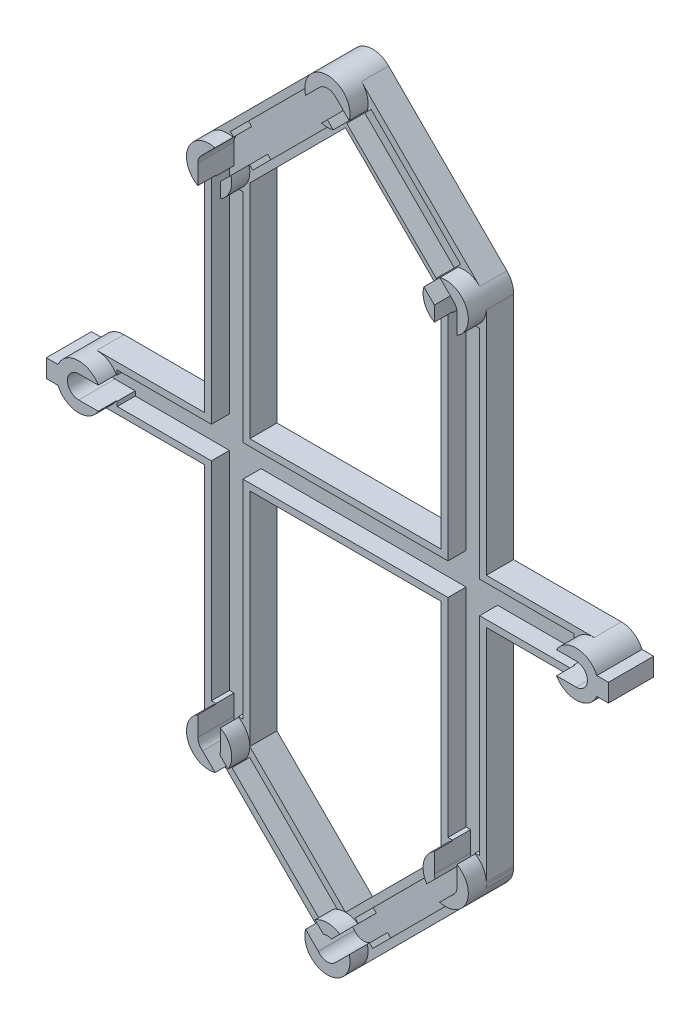
SolidWorks part; units mm, degrees
ref_plane "Спереди" through (0, 0, 0) normal (0, 0, 1) x (1, 0, 0)
ref_plane "Сверху" through (0, 0, 0) normal (0, 1, 0) x (1, 0, 0)
ref_plane "Справа" through (0, 0, 0) normal (1, 0, 0) x (0, 0, -1)
sketch "Эскиз1" plane through (0, 0, 0) normal (0, 0, 1) x (1, 0, 0)
  line L0 (-73.4107, 0) -> (65.3283, 0) construction
  line L1 (-12.0859, 54.2949) -> (-38.2489, 28.1319) construction
  line L2 (-12.0859, 54.2949) -> (14.077, 28.1319) construction
  line L3 (-38.2489, 0) -> (-38.2489, -121.4673) construction
  line L4 (14.077, 0) -> (14.077, -116.0096) construction
  line L5 (-38.2489, -81.8681) -> (14.077, -81.8681) construction
  line L6 (14.077, -81.8681) -> (-12.0859, -108.031) construction
  circle A0 centre (-12.0859, 54.2949) radius 2.5
  circle A1 centre (-12.0859, 54.2949) radius 5
  circle A2 centre (-38.2489, 28.1319) radius 2.5
  circle A3 centre (-38.2489, 28.1319) radius 5
  circle A4 centre (14.077, 28.1319) radius 2.5
  circle A5 centre (14.077, 28.1319) radius 5
  circle A6 centre (-38.2489, -81.8681) radius 2.5
  circle A7 centre (-38.2489, -81.8681) radius 5
  circle A8 centre (14.077, -81.8681) radius 2.5
  circle A9 centre (14.077, -81.8681) radius 5
  circle A10 centre (-12.0859, -108.031) radius 2.5
  circle A11 centre (-12.0859, -108.031) radius 5
  dimension "D2" = 5
  dimension "D3" = 10
  dimension "D5" = 45
  dimension "D1" = 45
  dimension "D4" = 37
  dimension "D6" = 37
  dimension "D7" = 110
  dimension "D8" = 110
  dimension "D9" = 37
  dimension "D10" = 45
  dimension "D11" = 37
extrude "Бобышка-Вытянуть1" add sketch "Эскиз1" along normal blind 10
sketch "Эскиз3" plane through (0, 0, 0) normal (0, 0, -1) x (-1, 0, 0)
  line L0 (12.0859, 54.2949) -> (15.6215, 57.8304)
  line L1 (15.6215, 57.8304) -> (41.7844, 31.6674)
  line L2 (41.7844, 31.6674) -> (34.7133, 24.5964)
  line L3 (34.7133, 24.5964) -> (8.5504, 50.7593)
  line L4 (8.5504, 50.7593) -> (12.0859, 54.2949)
  circle A0 centre (12.0859, 54.2949) radius 5 construction
  circle A1 centre (38.2489, 28.1319) radius 5 construction
extrude "Бобышка-Вытянуть2" add sketch "Эскиз3" against normal blind 6
sketch "Эскиз4" plane through (0, 0, 6) normal (0, 0, 1) x (1, 0, 0)
  line L0 (-13.8537, 56.0626) -> (-10.3181, 52.5271)
  line L1 (-13.8537, 56.0626) -> (-10.3181, 52.5271) construction
  line L2 (-10.3181, 52.5271) -> (-36.4811, 26.3641)
  line L3 (-36.4811, 26.3641) -> (-40.0166, 29.8997) construction
  line L4 (-36.4811, 26.3641) -> (-40.0166, 29.8997)
  line L5 (-40.0166, 29.8997) -> (-13.8537, 56.0626)
  line L6 (-8.5504, 50.7593) -> (-34.7133, 24.5964) construction
  line L8 (-41.7844, 31.6674) -> (-15.6215, 57.8304) construction
  dimension "D1" = 2.5
  dimension "D2" = 2.5
sketch "Эскиз9" plane through (0, 0, 0) normal (0, 0, -1) x (-1, 0, 0)
  line L0 (-14.077, 28.1319) -> (-17.6126, 31.6674)
  line L1 (-17.6126, 31.6674) -> (8.5504, 57.8304)
  line L2 (8.5504, 57.8304) -> (15.6215, 50.7593)
  line L3 (15.6215, 50.7593) -> (-10.5415, 24.5964)
  line L4 (-10.5415, 24.5964) -> (-14.077, 28.1319)
  circle A0 centre (-14.077, 28.1319) radius 5 construction
  arc A1 (15.6215, 57.8304) -> (8.5504, 50.7593) centre (12.0859, 54.2949) ccw construction
extrude "Бобышка-Вытянуть4" add sketch "Эскиз9" against normal blind 6
extrude "Вырез-Вытянуть1" cut sketch "Эскиз4" against normal blind 4
sketch "Эскиз5" plane through (0, 0, 0) normal (0, 0, -1) x (-1, 0, 0)
  line L0 (13.8537, 56.0626) -> (12.0859, 54.2949) construction
  line L1 (36.4811, 26.3641) -> (40.0166, 29.8997) construction
  circle A0 centre (12.9698, 55.1787) radius 3.75
  circle A1 centre (38.2489, 28.1319) radius 2.5
  arc A2 (36.4811, 26.3641) -> (40.0166, 29.8997) centre (38.2489, 28.1319) ccw construction
  arc A3 (13.8537, 56.0626) -> (10.3181, 56.0626) centre (12.0859, 54.2949) ccw construction
extrude "Бобышка-Вытянуть3" add sketch "Эскиз5" against normal blind 2
extrude "Вырез-Вытянуть2" cut sketch "Эскиз4<2>" along normal blind 4
sketch "Эскиз4<2>" plane through (0, 0, 6) normal (0, 0, 1) x (1, 0, 0) same geometry as "Эскиз4"
sketch "Эскиз10" plane through (0, 0, 10) normal (0, 0, 1) x (1, 0, 0)
  line L0 (14.077, 28.1319) -> (12.3093, 26.3641)
  line L1 (12.3093, 26.3641) -> (-13.8537, 52.5271)
  line L2 (-13.8537, 52.5271) -> (-12.0859, 54.2949)
  line L3 (-12.0859, 54.2949) -> (-10.3181, 56.0626)
  line L4 (-10.3181, 56.0626) -> (15.8448, 29.8997)
  line L5 (15.8448, 29.8997) -> (14.077, 28.1319)
  circle A0 centre (14.077, 28.1319) radius 2.5 construction
  arc A1 (-10.3181, 52.5271) -> (-13.8537, 56.0626) centre (-12.0859, 54.2949) ccw construction
extrude "Вырез-Вытянуть3" cut sketch "Эскиз10" against normal blind 8
sketch "Эскиз11" plane through (0, 0, 0) normal (0, 0, -1) x (-1, 0, 0)
  line L0 (-15.8448, 29.8997) -> (-12.3093, 26.3641) construction
  circle A0 centre (-14.077, 28.1319) radius 2.5
  arc A1 (-15.8448, 29.8997) -> (-12.3093, 26.3641) centre (-14.077, 28.1319) ccw construction
extrude "Бобышка-Вытянуть9" add sketch "Эскиз11" against normal blind 2
sketch "Skizze2" plane through (0, 0, 0) normal (0, 0, -1) x (-1, 0, 0)
  line L0 (-19.0722, 27.9121) -> (-19.0722, -82.053)
  line L1 (-18.9492, -82.9917) -> (-17.9635, -85.0138)
  line L2 (-17.9635, -85.0138) -> (8.5504, -111.5666)
  line L3 (8.5504, -111.5666) -> (15.6215, -111.5666)
  line L4 (15.6215, -111.5666) -> (41.7844, -85.4037)
  line L5 (41.7844, -85.4037) -> (43.2489, -81.8681)
  line L6 (43.2489, -81.8681) -> (43.2489, 28.1319)
  line L7 (33.2489, -81.8681) -> (33.2489, 26.0608)
  line L8 (12.0859, 47.2238) -> (34.7133, 24.5964) construction
  line L9 (33.2489, 26.0608) -> (43.2489, 28.1319)
  line L10 (33.2489, -81.8681) -> (12.0859, -103.031)
  line L11 (12.0859, -103.031) -> (-9.077, -81.8681)
  line L12 (-9.077, -81.8681) -> (-9.077, 26.0608)
  line L13 (-10.5415, 24.5964) -> (12.0859, 47.2238) construction
  line L14 (-9.077, 26.0608) -> (-19.0722, 27.9121)
  arc A0 (-17.6126, 31.6674) -> (-10.5415, 24.5964) centre (-14.077, 28.1319) ccw construction
  arc A1 (-19.0722, -82.053) -> (-18.9492, -82.9917) centre (-15.4304, -82.053) ccw
  circle A2 centre (-14.077, -81.8681) radius 5 construction
  circle A3 centre (12.0859, -108.031) radius 5 construction
  circle A4 centre (38.2489, -81.8681) radius 5 construction
  arc A5 (34.7133, 24.5964) -> (41.7844, 31.6674) centre (38.2489, 28.1319) ccw construction
extrude "Aufsatz-Linear austragen1" add sketch "Skizze2" against normal blind 6
sketch "Skizze4" plane through (0, 0, 10) normal (0, 0, 1) x (1, 0, 0)
  line L0 (11.577, -22.0611) -> (16.577, -22.0611)
  line L1 (16.577, -22.0611) -> (16.577, -81.8681)
  line L2 (16.577, -81.8681) -> (11.577, -81.8681)
  line L3 (11.577, -81.8681) -> (11.577, -22.0611)
  circle A0 centre (14.077, -81.8681) radius 2.5 construction
  circle A1 centre (14.077, -81.8681) radius 2.5 construction
extrude "Schnitt-Linear austragen1" cut sketch "Skizze4" against normal blind 8
sketch "Skizze5" plane through (0, 0, 10) normal (0, 0, 1) x (1, 0, 0)
  line L0 (-38.2489, -81.8681) -> (-35.7489, -81.8681)
  line L1 (-35.7489, -81.8681) -> (-35.7489, 28.1319)
  line L2 (-38.2489, -81.8681) -> (-40.7489, -81.8681)
  line L3 (-40.7489, -81.8681) -> (-40.7489, 28.1319)
  line L4 (-40.7489, 28.1319) -> (-35.7489, 28.1319)
  circle A0 centre (-38.2489, -81.8681) radius 2.5 construction
  arc A1 (-40.0166, 29.8997) -> (-40.6921, 27.6024) centre (-38.2489, 28.1319) ccw construction
extrude "Schnitt-Linear austragen2" cut sketch "Skizze5" against normal blind 8
sketch "Skizze6" plane through (0, 0, 10) normal (0, 0, 1) x (1, 0, 0)
  line L0 (-12.8158, -107.3468) -> (13.706, -80.7861)
  line L2 (13.706, -80.7861) -> (16.1827, -83.2591)
  line L3 (16.1827, -83.2591) -> (-10.3391, -109.8198)
  line L5 (-10.3391, -109.8198) -> (-12.8158, -107.3468)
  line L6 (17.2285, -85.7499) -> (-8.5478, -111.564) construction
  dimension "D1" = 2.5
  dimension "D2" = 3.5
extrude "Schnitt-Linear austragen3" cut sketch "Skizze6" against normal blind 8
sketch "Skizze8" plane through (0, 0, 10) normal (0, 0, 1) x (1, 0, 0)
  line L0 (-37.3688, -81.2837) -> (-11.1862, -107.4663)
  line L1 (-11.1862, -107.4663) -> (-13.6611, -109.9412)
  line L2 (-13.6611, -109.9412) -> (-39.8437, -83.7585)
  line L3 (-39.8437, -83.7585) -> (-37.3688, -81.2837)
  line L5 (-33.2489, -81.8681) -> (-12.0859, -103.031) construction
  dimension "D1" = 2.5
  dimension "D2" = 3.5
extrude "Schnitt-Linear austragen6" cut sketch "Skizze8" against normal blind 8
sketch "Skizze9" plane through (0, 0, 10) normal (0, 0, 1) x (1, 0, 0)
  line L1 (16.577, -22.0611) -> (11.577, -22.0611)
  line L2 (16.577, -22.0611) -> (16.577, 28.2549)
  line L3 (16.577, 28.2549) -> (11.577, 28.2549)
  line L4 (11.577, -22.0611) -> (11.577, 28.2549)
extrude "Schnitt-Linear austragen8" cut sketch "Skizze9" against normal blind 8
sketch "Skizze10" plane through (0, 0, 6) normal (0, 0, 1) x (1, 0, 0)
  line L2 (11.7397, -82.7552) -> (12.6255, -81.8681)
  line L3 (12.6255, -81.8681) -> (11.577, -81.8681)
  line L4 (11.7397, -82.7552) -> (12.6255, -81.8681)
  line L5 (12.6255, -81.8681) -> (11.577, -81.8681)
  line L6 (14.7896, -81.8681) -> (16.1656, -83.2421)
  line L7 (16.577, -81.8681) -> (14.7896, -81.8681)
  line L8 (14.7896, -81.8681) -> (16.1656, -83.2421)
  line L9 (16.577, -81.8681) -> (14.7896, -81.8681)
  line L10 (-12.9627, -105.6898) -> (-12.0613, -106.5912)
  line L11 (-12.0613, -106.5912) -> (-11.1745, -105.7031)
  line L12 (-12.9627, -105.6898) -> (-12.0613, -106.5912)
  line L13 (-12.0613, -106.5912) -> (-11.1745, -105.7031)
  line L14 (-36.7844, -81.8681) -> (-35.9076, -82.7448)
  line L15 (-11.9406, -108.2207) -> (-13.6611, -109.9412)
  line L16 (-13.6611, -109.9412) -> (-14.1255, -109.4767)
  line L17 (-10.3393, -109.8197) -> (-11.9406, -108.2207)
  line L18 (-11.9406, -108.2207) -> (-13.6611, -109.9412)
  line L19 (-13.6611, -109.9412) -> (-14.1255, -109.4767)
  line L20 (-10.3393, -109.8197) -> (-11.9406, -108.2207)
  line L21 (-39.8437, -83.7585) -> (-37.9533, -81.8681)
  line L22 (-37.9533, -81.8681) -> (-40.7489, -81.8681)
  line L23 (-39.6945, -83.9077) -> (-39.8437, -83.7585)
  line L24 (-39.8437, -83.7585) -> (-37.9533, -81.8681)
  line L25 (-37.9533, -81.8681) -> (-40.7489, -81.8681)
  line L26 (-39.6945, -83.9077) -> (-39.8437, -83.7585)
  line L27 (-35.7489, -81.8681) -> (-36.7844, -81.8681)
  line L28 (-36.7844, -81.8681) -> (-35.9076, -82.7448)
  line L29 (-35.7489, -81.8681) -> (-36.7844, -81.8681)
  arc A1 (11.577, -81.8681) -> (11.7397, -82.7552) centre (14.077, -81.8681) ccw
  arc A2 (11.577, -81.8681) -> (11.7397, -82.7552) centre (14.077, -81.8681) ccw
  arc A3 (16.1656, -83.2421) -> (16.577, -81.8681) centre (14.077, -81.8681) ccw
  arc A4 (16.1656, -83.2421) -> (16.577, -81.8681) centre (14.077, -81.8681) ccw
  arc A5 (-11.1745, -105.7031) -> (-12.9627, -105.6898) centre (-12.0859, -108.031) ccw
  arc A6 (-11.1745, -105.7031) -> (-12.9627, -105.6898) centre (-12.0859, -108.031) ccw
  arc A7 (-14.1255, -109.4767) -> (-10.3393, -109.8197) centre (-12.0859, -108.031) ccw
  arc A8 (-14.1255, -109.4767) -> (-10.3393, -109.8197) centre (-12.0859, -108.031) ccw
  arc A9 (-40.7489, -81.8681) -> (-39.6945, -83.9077) centre (-38.2489, -81.8681) ccw
  arc A10 (-40.7489, -81.8681) -> (-39.6945, -83.9077) centre (-38.2489, -81.8681) ccw
  arc A11 (-35.9076, -82.7448) -> (-35.7489, -81.8681) centre (-38.2489, -81.8681) ccw
  arc A12 (-35.9076, -82.7448) -> (-35.7489, -81.8681) centre (-38.2489, -81.8681) ccw
  dimension "D1" = 0
  dimension "D2" = 0
  dimension "D3" = 0
  dimension "D4" = 0
  dimension "D5" = 0
  dimension "D6" = 0
extrude "Schnitt-Linear austragen9" cut sketch "Skizze10" against normal blind 4
sketch "Skizze11" plane through (0, 0, 0) normal (0, 0, -1) x (-1, 0, 0)
  line L0 (12.0859, 47.2238) -> (12.0859, -103.031) construction
  line L2 (-42.9141, -22.9036) -> (67.0859, -22.9036)
  line L3 (-42.9141, -22.9036) -> (-42.9141, -32.9036)
  line L4 (-42.9141, -32.9036) -> (67.0859, -32.9036)
  line L5 (12.0859, 47.2238) -> (33.2489, 26.0608) construction
  line L6 (67.0859, -22.9036) -> (67.0859, -32.9036)
  point P9 (12.0859, -27.9036)
  dimension "D1" = 5
  dimension "D2" = 90
  dimension "D3" = 55
  dimension "D4" = 10
  dimension "D5" = 110
extrude "Aufsatz-Linear austragen2" add sketch "Skizze11" against normal blind 6
sketch "Skizze12" plane through (0, 0, 0) normal (0, 0, -1) x (-1, 0, 0)
  line L0 (67.0859, -22.9036) -> (43.2489, -22.9036) construction
  line L1 (67.0859, -32.9036) -> (67.0859, -22.9036) construction
  line L2 (-42.9141, -22.9036) -> (-42.9141, -32.9036) construction
  line L3 (-42.9141, -32.9036) -> (-19.0722, -32.9036) construction
  circle A0 centre (-42.9141, -27.9036) radius 2.5
  circle A1 centre (-42.9141, -27.9036) radius 5
  circle A2 centre (67.0859, -27.9036) radius 2.5
  circle A3 centre (67.0859, -27.9036) radius 5
  dimension "D1" = 5
  dimension "D2" = 10
  dimension "D5" = 5
  dimension "D6" = 10
  dimension "D3" = 5
  dimension "D4" = 0
  dimension "D7" = 0
  dimension "D8" = 5
extrude "Aufsatz-Linear austragen4" add sketch "Skizze12" against normal blind 10
sketch "Skizze15" plane through (0, 0, 10) normal (0, 0, 1) x (1, 0, 0)
  line L0 (42.9141, -30.4036) -> (16.602, -30.4036)
  line L1 (16.602, -30.4036) -> (16.577, -32.9036)
  line L2 (16.577, -32.9036) -> (11.577, -32.9036)
  line L3 (11.577, -32.9036) -> (11.577, -81.8681) construction
  line L4 (16.577, -32.9036) -> (11.577, -32.9036) construction
  line L5 (11.577, -32.9036) -> (11.577, -30.4036)
  line L6 (11.577, -30.4036) -> (-35.7489, -30.4036)
  line L7 (-35.7489, -30.4036) -> (-35.7489, -32.9036)
  line L8 (-35.7489, -32.9036) -> (-40.7489, -32.9036)
  line L9 (-40.7489, -32.9036) -> (-40.7489, -30.4036)
  line L10 (-40.7489, -30.4036) -> (-67.0859, -30.4036)
  line L11 (-67.0859, -30.4036) -> (-67.0859, -25.4036)
  line L12 (-67.0859, -25.4036) -> (-40.7489, -25.4036)
  line L13 (-40.7489, -25.4036) -> (-40.7489, -22.9036)
  line L14 (-40.7489, -22.9036) -> (-35.7489, -22.9036)
  line L15 (-35.7489, -22.9036) -> (-35.7489, -25.4036)
  line L16 (-35.7489, -25.4036) -> (11.577, -25.4036)
  line L17 (11.577, -25.4036) -> (11.577, -22.9036)
  line L18 (11.577, -22.9036) -> (16.577, -22.9036)
  line L19 (16.577, -22.9036) -> (16.577, -25.4036)
  line L20 (16.577, -25.4036) -> (42.9141, -25.4036)
  line L21 (42.9141, -25.4036) -> (42.9141, -30.4036)
  circle A0 centre (-67.0859, -27.9036) radius 2.5 construction
  arc A1 (-67.0859, -30.4036) -> (-67.0859, -25.4036) centre (-67.0859, -27.9036) ccw construction
extrude "Schnitt-Linear austragen10" cut sketch "Skizze15" against normal blind 8
sketch "Skizze16" plane through (0, 0, 0) normal (0, 0, -1) x (-1, 0, 0)
  line L0 (67.0859, -30.4036) -> (67.0859, -25.4036) construction
  line L1 (67.0859, -30.4036) -> (67.0859, -25.4036)
  line L2 (-42.9141, -25.4036) -> (-42.9141, -30.4036) construction
  line L3 (-42.9141, -25.4036) -> (-42.9141, -30.4036)
  arc A0 (67.0859, -30.4036) -> (67.0859, -25.4036) centre (67.0859, -27.9036) ccw construction
  arc A1 (67.0859, -30.4036) -> (67.0859, -25.4036) centre (67.0859, -27.9036) ccw
  arc A2 (-42.9141, -25.4036) -> (-42.9141, -30.4036) centre (-42.9141, -27.9036) ccw construction
  arc A3 (-42.9141, -25.4036) -> (-42.9141, -30.4036) centre (-42.9141, -27.9036) ccw
extrude "Aufsatz-Linear austragen5" add sketch "Skizze16" against normal blind 2
sketch "Skizze17" plane through (0, 0, 0) normal (0, 0, -1) x (-1, 0, 0)
  line L0 (-19.0722, -22.9036) -> (-42.9141, -22.9036) construction
  line L1 (-47.0722, -25.9036) -> (-50.0722, -25.9036)
  line L2 (-47.0722, -25.9036) -> (-47.0722, -29.9036)
  line L3 (-47.0722, -29.9036) -> (-50.0722, -29.9036)
  line L4 (-50.0722, -25.9036) -> (-50.0722, -29.9036)
  line L5 (-42.9141, -32.9036) -> (-19.0722, -32.9036) construction
  line L6 (-19.0722, -32.9036) -> (-19.0722, -81.6482) construction
  line L7 (67.0859, -22.9036) -> (43.2489, -22.9036) construction
  line L8 (71.2489, -25.9036) -> (74.2489, -25.9036)
  line L9 (71.2489, -25.9036) -> (71.2489, -29.9036)
  line L10 (71.2489, -29.9036) -> (74.2489, -29.9036)
  line L11 (74.2489, -25.9036) -> (74.2489, -29.9036)
  line L12 (43.2489, -32.9036) -> (67.0859, -32.9036) construction
  line L13 (43.2489, -81.8681) -> (43.2489, -32.9036) construction
  dimension "D1" = 3
  dimension "D2" = 3
  dimension "D3" = 28
  dimension "D4" = 3
  dimension "D5" = 3
  dimension "D6" = 3
  dimension "D7" = 28
  dimension "D8" = 3
extrude "Aufsatz-Linear austragen6" add sketch "Skizze17" against normal blind 10
sketch "Skizze18" plane through (0, 0, 6) normal (0, 0, 1) x (1, 0, 0)
  line L0 (-43.2489, -32.9036) -> (-67.0859, -32.9036) construction
  line L1 (38.4141, -24.4036) -> (-62.5764, -24.4036)
  line L2 (38.4141, -24.4036) -> (38.4141, -31.4036)
  line L3 (38.4141, -31.4036) -> (-62.5764, -31.4036)
  line L4 (-62.5764, -24.4036) -> (-62.5764, -31.4036)
  line L5 (-67.0859, -22.9036) -> (-43.2489, -22.9036) construction
  arc A0 (-67.0859, -25.4036) -> (-67.0859, -30.4036) centre (-67.0859, -27.9036) ccw construction
  arc A1 (42.9141, -30.4036) -> (42.9141, -25.4036) centre (42.9141, -27.9036) ccw construction
  point P11 (-69.5859, -27.9036)
  dimension "D1" = 1.5
  dimension "D2" = 1.5
  dimension "D3" = 7.0096
  dimension "D4" = 4.5
extrude "Schnitt-Linear austragen11" cut sketch "Skizze18" against normal blind 4
sketch "Skizze19" plane through (0, 0, 6) normal (0, 0, 1) x (1, 0, 0)
  line L0 (-33.2489, 26.0608) -> (-33.2489, -22.9036) construction
  line L1 (-34.7489, 23.6319) -> (-41.7489, 23.6319)
  line L2 (-34.7489, 23.6319) -> (-34.7489, -77.3681)
  line L3 (-34.7489, -77.3681) -> (-41.7489, -77.3681)
  line L4 (-41.7489, 23.6319) -> (-41.7489, -77.3681)
  line L5 (-43.2489, -22.9036) -> (-43.2489, 28.1319) construction
  line L6 (19.0722, 27.9121) -> (19.0722, -22.9036) construction
  line L7 (17.5722, 23.6319) -> (10.577, 23.6319)
  line L8 (17.5722, 23.6319) -> (17.5722, -77.3681)
  line L9 (17.5722, -77.3681) -> (10.577, -77.3681)
  line L10 (10.577, 23.6319) -> (10.577, -77.3681)
  line L11 (9.077, -22.9036) -> (9.077, 26.0608) construction
  arc A0 (-36.9548, 32.9615) -> (-40.7489, 23.8018) centre (-38.2489, 28.1319) ccw construction
  arc A1 (-40.7489, -77.538) -> (-36.9153, -86.687) centre (-38.2489, -81.8681) ccw construction
  arc A2 (16.577, 23.8018) -> (12.7829, 32.9615) centre (14.077, 28.1319) ccw construction
  arc A3 (12.7563, -86.6905) -> (16.577, -77.538) centre (14.077, -81.8681) ccw construction
  dimension "D1" = 1.5
  dimension "D2" = 1.5
  dimension "D3" = 4.5
  dimension "D4" = 4.5
  dimension "D5" = 1.5
  dimension "D6" = 1.5
  dimension "D7" = 4.5
  dimension "D8" = 4.5
extrude "Schnitt-Linear austragen12" cut sketch "Skizze19" against normal blind 4
sketch "Skizze20" plane through (0, 0, 6) normal (0, 0, 1) x (1, 0, 0)
  line L0 (13.3549, -87.5063) -> (-6.0763, -106.966)
  line L1 (-6.0763, -106.966) -> (-9.9682, -103.0797)
  line L2 (-9.9682, -103.0797) -> (9.4629, -83.6201)
  line L3 (9.4629, -83.6201) -> (13.3549, -87.5063)
  line L4 (17.2285, -85.7499) -> (-8.5478, -111.564) construction
  line L6 (-33.274, -83.9643) -> (-13.8286, -103.4097)
  line L7 (-13.8286, -103.4097) -> (-17.7428, -107.3239)
  line L8 (-17.7428, -107.3239) -> (-37.1882, -87.8785)
  line L9 (-37.1882, -87.8785) -> (-33.274, -83.9643)
  line L10 (-33.2489, -81.8681) -> (-12.0859, -103.031) construction
  line L11 (-15.6215, -111.5666) -> (-41.7844, -85.4037) construction
  arc A0 (12.7563, -86.6905) -> (16.577, -77.538) centre (14.077, -81.8681) ccw construction
  arc A1 (-16.9048, -106.6975) -> (-7.2572, -106.7334) centre (-12.0859, -108.031) ccw construction
  arc A2 (-40.7489, -77.538) -> (-36.9153, -86.687) centre (-38.2489, -81.8681) ccw construction
  dimension "D1" = 1.5
  dimension "D2" = 4.5
  dimension "D3" = 5.5
  dimension "D4" = 5
  dimension "D5" = 1.5
  dimension "D6" = 1.5
  dimension "D7" = 4.5
  dimension "D8" = 5
extrude "Schnitt-Linear austragen13" cut sketch "Skizze20" against normal blind 4
sketch "Skizze21" plane through (0, 0, 6) normal (0, 0, 1) x (1, 0, 0)
  line L0 (-11.8121, 48.2047) -> (7.9869, 28.4057)
  line L1 (7.9869, 28.4057) -> (13.3699, 33.7888)
  line L2 (13.3699, 33.7888) -> (-6.4291, 53.5878)
  line L3 (-6.4291, 53.5878) -> (-11.8121, 48.2047)
  line L4 (-17.7428, 53.5878) -> (-12.793, 48.638)
  line L5 (-12.793, 48.638) -> (-32.592, 28.839)
  line L6 (-32.592, 28.839) -> (-37.5418, 33.7888)
  line L7 (-37.5418, 33.7888) -> (-17.7428, 53.5878)
  line L8 (-8.5504, 57.8304) -> (17.6126, 31.6674) construction
  line L9 (9.077, 26.0608) -> (-12.0859, 47.2238) construction
  line L10 (-12.0859, 47.2238) -> (-33.2489, 26.0608) construction
  line L11 (-41.7844, 31.6674) -> (-15.6215, 57.8304) construction
  arc A0 (16.577, 23.8018) -> (12.7829, 32.9615) centre (14.077, 28.1319) ccw construction
  arc A1 (-7.2563, 53.0008) -> (-16.9155, 53.0008) centre (-12.0859, 54.2949) ccw construction
  arc A2 (-36.9548, 32.9615) -> (-40.7489, 23.8018) centre (-38.2489, 28.1319) ccw construction
  dimension "D1" = 1.5
  dimension "D2" = 0.8872
  dimension "D3" = 1.5
  dimension "D4" = 1.5
  dimension "D5" = 4.5
  dimension "D6" = 4.5
  dimension "D7" = 4.5
  dimension "D8" = 4.5
extrude "Schnitt-Linear austragen14" cut sketch "Skizze21" against normal blind 4
